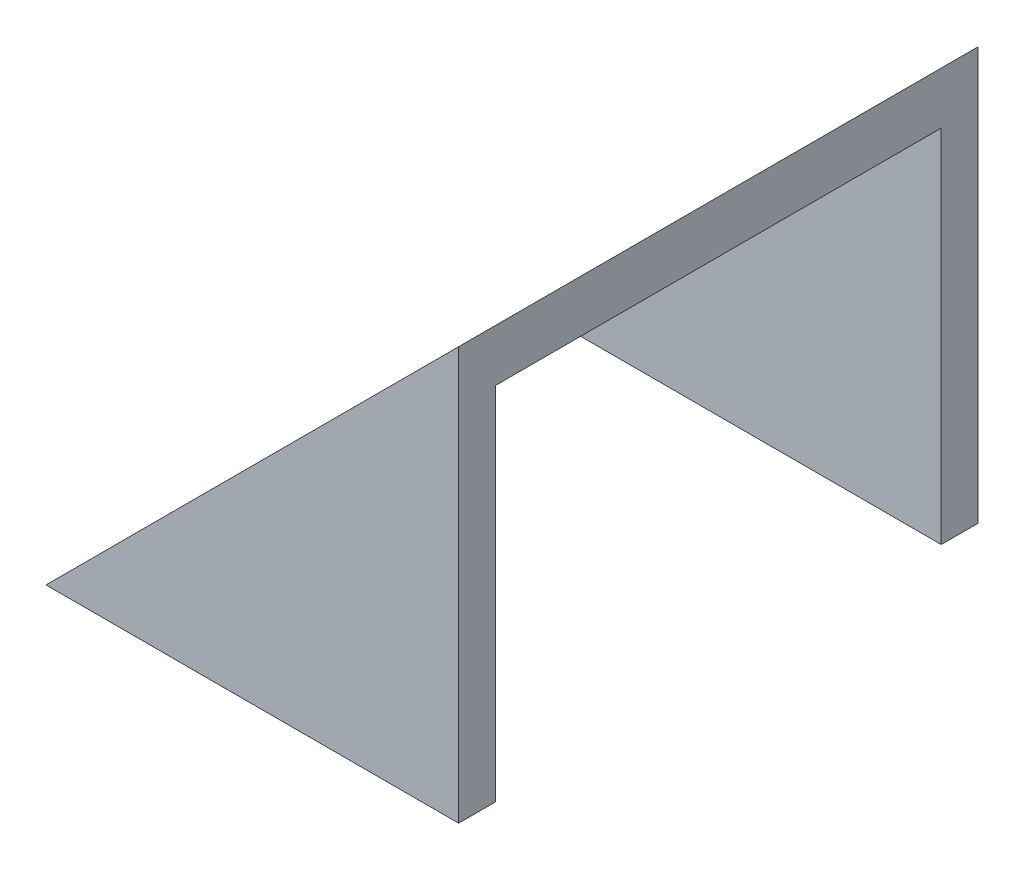
SolidWorks part; units mm, degrees
ref_plane "Front Plane" through (0, 0, 0) normal (0, 0, 1) x (1, 0, 0)
ref_plane "Top Plane" through (0, 0, 0) normal (0, 1, 0) x (1, 0, 0)
ref_plane "Right Plane" through (0, 0, 0) normal (1, 0, 0) x (0, 0, -1)
sketch "Sketch1" plane through (0, 0, 0) normal (0, 0, 1) x (1, 0, 0)
  line L0 (0, 0) -> (17.9605, 17.9605)
  line L1 (17.9605, 17.9605) -> (17.9605, 0)
  line L2 (17.9605, 0) -> (0, 0)
  dimension "D1" = 25.4
  dimension "D2" = 45
extrude "Boss-Extrude1" add sketch "Sketch1" along normal blind 22.606
sketch "Sketch2" plane through (17.9605, 0, 0) normal (1, 0, 0) x (0, 0, -1)
  line L7 (-21.006, 0) -> (-1.6, 0)
  line L10 (-1.6, 0) -> (-1.6, 16.3605)
  line L11 (-21.006, 16.3605) -> (-21.006, 0)
  line L12 (-1.6, 16.3605) -> (-21.006, 16.3605)
  line L13 (-1.6, 0) -> (-1.6, 16.3605)
  line L14 (-21.006, 16.3605) -> (-21.006, 0)
  line L15 (-1.6, 16.3605) -> (-21.006, 16.3605)
  dimension "D1" = 1.6
extrude "Cut-Extrude1" cut sketch "Sketch2" against normal offset from surface (15.6978 mm away) 1.6 up to face at (8.9803, 8.9803, 11.303)
